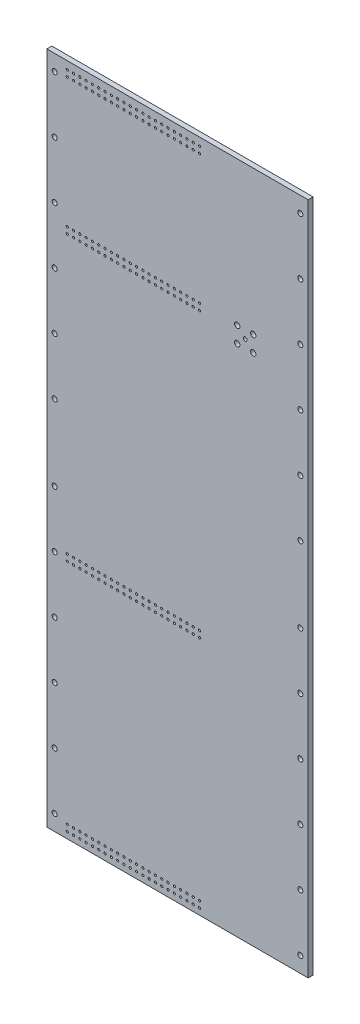
SolidWorks part; units mm, degrees
ref_plane "Front Plane" through (0, 0, 0) normal (0, 0, 1) x (1, 0, 0)
ref_plane "Top Plane" through (0, 0, 0) normal (0, 1, 0) x (1, 0, 0)
ref_plane "Right Plane" through (0, 0, 0) normal (1, 0, 0) x (0, 0, -1)
sketch "Sketch1" plane through (0, 0, 0) normal (0, 0, 1) x (1, 0, 0)
  line L1 (-41.5, -107) -> (41.5, -107)
  line L2 (-41.5, -107) -> (-41.5, 107)
  line L3 (-41.5, 107) -> (41.5, 107)
  line L4 (41.5, -107) -> (41.5, 107)
  line L5 (-41.5, -107) -> (41.5, 107) construction
  line L6 (-41.5, 107) -> (41.5, -107) construction
  point P0 (0, 0)
  dimension "D1" = 83
  dimension "D2" = 214
extrude "Boss-Extrude1" add sketch "Sketch1" along normal blind 1.5875
hole_wizard "#0 Clearance Hole1" positions "Sketch5" profile "Sketch3" hole size "#0" standard "ANSI Inch"
sketch "Sketch5" plane through (0, 0, 1.5875) normal (0, 0, 1) x (1, 0, 0)
  line L0 (0, 0) -> (0, 107) construction
  line L1 (41.5, 107) -> (-41.5, 107) construction
  line L4 (-41.5, 107) -> (-41.5, -107) construction
  line L5 (-41.5, 0) -> (41.5, 0) construction
  line L6 (41.5, -107) -> (41.5, 107) construction
  line L8 (-41.5, 7) -> (41.5, 7) construction
  line L9 (-41.5, 7) -> (-41.5, 107) construction
  line L10 (-41.5, 107) -> (41.5, 107) construction
  line L11 (41.5, 7) -> (41.5, 107) construction
  point P490 (-39, 102)
  point P557 (39, 102)
  point P558 (39, 84)
  point P559 (39, 66)
  point P560 (39, 48)
  point P561 (39, 30)
  point P562 (39, 12)
  point P563 (-39, 84)
  point P564 (-39, 66)
  point P565 (-39, 48)
  point P566 (-39, 30)
  point P567 (-39, 12)
  dimension "D1" = 2.5
  dimension "D2" = 6
  dimension "D4" = 2.5
  dimension "D3" = 2
  dimension "D5" = 100
  dimension "D6" = 5
  dimension "D7" = 5
sketch "Sketch3" plane through (-39, 102, 1.5875) normal (1, 0, 0) x (0, -1, 0)
  line L0 (0, 0) -> (0, 3.6596)
  line L1 (0, 3.6596) -> (0.8064, 3.175)
  line L2 (0.8064, 3.175) -> (0.8064, 0)
  line L5 (0.8064, 0) -> (0, 0)
  line L10 (0, 3.6596) -> (-0.8065, 3.175) construction
  line L11 (0, -6.35) -> (0, 107.95) construction
  dimension "Hole Dia." = 1.6129
  dimension "Hole Depth" = 3.175
  dimension "Drill Angle" = 118
sketch "Sketch6" plane through (0, 0, 0) normal (0, 0, -1) x (-1, 0, 0)
  line L0 (41.5, -7) -> (-41.5, -7) construction
  line L1 (-36.2, 0) -> (36.3, 0)
  line L2 (-36.2, 0) -> (-36.2, -7)
  line L3 (-36.2, -7) -> (36.3, -7)
  line L4 (36.3, 0) -> (36.3, -7)
  dimension "D1" = 72.5
extrude "Boss-Extrude3" add sketch "Sketch6" along normal blind 4.9125
sketch "Sketch7" plane through (0, 0, 1.5875) normal (0, 0, 1) x (1, 0, 0)
  line L0 (0, 107) -> (0, -107) construction
  line L1 (41.5, 107) -> (-41.5, 107) construction
  line L2 (-41.5, -107) -> (41.5, -107) construction
  line L3 (-36, 62.325) -> (8, 62.325) construction
  line L4 (-36, 105.5) -> (8, 105.5) construction
  line L5 (-36, 105.5) -> (-36, 101.5) construction
  line L6 (-36, 101.5) -> (8, 101.5) construction
  line L7 (8, 105.5) -> (8, 101.5) construction
  line L8 (-36, 62.325) -> (-36, 58.325) construction
  line L9 (-36, 58.325) -> (8, 58.325) construction
  line L10 (8, 62.325) -> (8, 58.325) construction
  line L11 (-36, 60.325) -> (41.5, 60.325) construction
  line L12 (41.5, -107) -> (41.5, 107) construction
  line L13 (-36, -27.675) -> (8, -27.675) construction
  line L14 (18, 62.206) -> (25, 62.206) construction
  line L15 (18, 62.206) -> (18, 55.206) construction
  line L16 (18, 55.206) -> (25, 55.206) construction
  line L17 (25, 62.206) -> (25, 55.206) construction
  line L18 (-36, -27.675) -> (-36, -31.675) construction
  line L19 (-36, -31.675) -> (8, -31.675) construction
  line L20 (8, -27.675) -> (8, -31.675) construction
  line L21 (-36, -102) -> (8, -102) construction
  line L22 (-36, -102) -> (-36, -106) construction
  line L23 (-36, -106) -> (8, -106) construction
  line L24 (8, -102) -> (8, -106) construction
  circle A0 centre (-35, 102.5) radius 0.35
  circle A1 centre (-33, 102.5) radius 0.35
  circle A2 centre (-31, 102.5) radius 0.35
  circle A3 centre (-29, 102.5) radius 0.35
  circle A4 centre (-27, 102.5) radius 0.35
  circle A5 centre (-25, 102.5) radius 0.35
  circle A6 centre (-23, 102.5) radius 0.35
  circle A7 centre (-21, 102.5) radius 0.35
  circle A8 centre (-19, 102.5) radius 0.35
  circle A9 centre (-17, 102.5) radius 0.35
  circle A10 centre (-15, 102.5) radius 0.35
  circle A11 centre (-13, 102.5) radius 0.35
  circle A12 centre (-11, 102.5) radius 0.35
  circle A13 centre (-9, 102.5) radius 0.35
  circle A14 centre (-7, 102.5) radius 0.35
  circle A15 centre (-5, 102.5) radius 0.35
  circle A16 centre (-3, 102.5) radius 0.35
  circle A17 centre (-1, 102.5) radius 0.35
  circle A18 centre (1, 102.5) radius 0.35
  circle A19 centre (3, 102.5) radius 0.35
  circle A20 centre (5, 102.5) radius 0.35
  circle A21 centre (7, 102.5) radius 0.35
  circle A22 centre (-33, 104.5) radius 0.35
  circle A23 centre (-31, 104.5) radius 0.35
  circle A24 centre (-29, 104.5) radius 0.35
  circle A25 centre (-27, 104.5) radius 0.35
  circle A26 centre (-25, 104.5) radius 0.35
  circle A27 centre (-23, 104.5) radius 0.35
  circle A28 centre (-21, 104.5) radius 0.35
  circle A29 centre (-19, 104.5) radius 0.35
  circle A30 centre (-17, 104.5) radius 0.35
  circle A31 centre (-15, 104.5) radius 0.35
  circle A32 centre (-13, 104.5) radius 0.35
  circle A33 centre (-11, 104.5) radius 0.35
  circle A34 centre (-9, 104.5) radius 0.35
  circle A35 centre (-7, 104.5) radius 0.35
  circle A36 centre (-5, 104.5) radius 0.35
  circle A37 centre (-3, 104.5) radius 0.35
  circle A38 centre (-1, 104.5) radius 0.35
  circle A39 centre (1, 104.5) radius 0.35
  circle A40 centre (3, 104.5) radius 0.35
  circle A41 centre (5, 104.5) radius 0.35
  circle A42 centre (7, 104.5) radius 0.35
  circle A43 centre (-35, 104.5) radius 0.35
  circle A44 centre (-35, 59.325) radius 0.35
  circle A45 centre (-33, 59.325) radius 0.35
  circle A46 centre (-31, 59.325) radius 0.35
  circle A47 centre (-29, 59.325) radius 0.35
  circle A48 centre (-27, 59.325) radius 0.35
  circle A49 centre (-25, 59.325) radius 0.35
  circle A50 centre (-23, 59.325) radius 0.35
  circle A51 centre (-21, 59.325) radius 0.35
  circle A52 centre (-19, 59.325) radius 0.35
  circle A53 centre (-17, 59.325) radius 0.35
  circle A54 centre (-15, 59.325) radius 0.35
  circle A55 centre (-13, 59.325) radius 0.35
  circle A56 centre (-11, 59.325) radius 0.35
  circle A57 centre (-9, 59.325) radius 0.35
  circle A58 centre (-7, 59.325) radius 0.35
  circle A59 centre (-5, 59.325) radius 0.35
  circle A60 centre (-3, 59.325) radius 0.35
  circle A61 centre (-1, 59.325) radius 0.35
  circle A62 centre (1, 59.325) radius 0.35
  circle A63 centre (3, 59.325) radius 0.35
  circle A64 centre (5, 59.325) radius 0.35
  circle A65 centre (7, 59.325) radius 0.35
  circle A66 centre (-33, 61.325) radius 0.35
  circle A67 centre (-31, 61.325) radius 0.35
  circle A68 centre (-29, 61.325) radius 0.35
  circle A69 centre (-27, 61.325) radius 0.35
  circle A70 centre (-25, 61.325) radius 0.35
  circle A71 centre (-23, 61.325) radius 0.35
  circle A72 centre (-21, 61.325) radius 0.35
  circle A73 centre (-19, 61.325) radius 0.35
  circle A74 centre (-17, 61.325) radius 0.35
  circle A75 centre (-15, 61.325) radius 0.35
  circle A76 centre (-13, 61.325) radius 0.35
  circle A77 centre (-11, 61.325) radius 0.35
  circle A78 centre (-9, 61.325) radius 0.35
  circle A79 centre (-7, 61.325) radius 0.35
  circle A80 centre (-5, 61.325) radius 0.35
  circle A81 centre (-3, 61.325) radius 0.35
  circle A82 centre (-1, 61.325) radius 0.35
  circle A83 centre (1, 61.325) radius 0.35
  circle A84 centre (3, 61.325) radius 0.35
  circle A85 centre (5, 61.325) radius 0.35
  circle A86 centre (7, 61.325) radius 0.35
  circle A87 centre (-35, 61.325) radius 0.35
  circle A88 centre (21.5, 58.706) radius 0.6
  circle A89 centre (18.96, 61.246) radius 0.85
  circle A90 centre (24.04, 61.246) radius 0.85
  circle A91 centre (24.04, 56.166) radius 0.85
  circle A92 centre (18.96, 56.166) radius 0.85
  circle A93 centre (21.5, 58.706) radius 0.381 construction
  circle A94 centre (-35, -30.675) radius 0.35
  circle A95 centre (-33, -30.675) radius 0.35
  circle A96 centre (-31, -30.675) radius 0.35
  circle A97 centre (-29, -30.675) radius 0.35
  circle A98 centre (-27, -30.675) radius 0.35
  circle A99 centre (-25, -30.675) radius 0.35
  circle A100 centre (-23, -30.675) radius 0.35
  circle A101 centre (-21, -30.675) radius 0.35
  circle A102 centre (-19, -30.675) radius 0.35
  circle A103 centre (-17, -30.675) radius 0.35
  circle A104 centre (-15, -30.675) radius 0.35
  circle A105 centre (-13, -30.675) radius 0.35
  circle A106 centre (-11, -30.675) radius 0.35
  circle A107 centre (-9, -30.675) radius 0.35
  circle A108 centre (-7, -30.675) radius 0.35
  circle A109 centre (-5, -30.675) radius 0.35
  circle A110 centre (-3, -30.675) radius 0.35
  circle A111 centre (-1, -30.675) radius 0.35
  circle A112 centre (1, -30.675) radius 0.35
  circle A113 centre (3, -30.675) radius 0.35
  circle A114 centre (5, -30.675) radius 0.35
  circle A115 centre (7, -30.675) radius 0.35
  circle A116 centre (-33, -28.675) radius 0.35
  circle A117 centre (-31, -28.675) radius 0.35
  circle A118 centre (-29, -28.675) radius 0.35
  circle A119 centre (-27, -28.675) radius 0.35
  circle A120 centre (-25, -28.675) radius 0.35
  circle A121 centre (-23, -28.675) radius 0.35
  circle A122 centre (-21, -28.675) radius 0.35
  circle A123 centre (-19, -28.675) radius 0.35
  circle A124 centre (-17, -28.675) radius 0.35
  circle A125 centre (-15, -28.675) radius 0.35
  circle A126 centre (-13, -28.675) radius 0.35
  circle A127 centre (-11, -28.675) radius 0.35
  circle A128 centre (-9, -28.675) radius 0.35
  circle A129 centre (-7, -28.675) radius 0.35
  circle A130 centre (-5, -28.675) radius 0.35
  circle A131 centre (-3, -28.675) radius 0.35
  circle A132 centre (-1, -28.675) radius 0.35
  circle A133 centre (1, -28.675) radius 0.35
  circle A134 centre (3, -28.675) radius 0.35
  circle A135 centre (5, -28.675) radius 0.35
  circle A136 centre (7, -28.675) radius 0.35
  circle A137 centre (-35, -28.675) radius 0.35
  circle A138 centre (-35, -105) radius 0.35
  circle A139 centre (-33, -105) radius 0.35
  circle A140 centre (-31, -105) radius 0.35
  circle A141 centre (-29, -105) radius 0.35
  circle A142 centre (-27, -105) radius 0.35
  circle A143 centre (-25, -105) radius 0.35
  circle A144 centre (-23, -105) radius 0.35
  circle A145 centre (-21, -105) radius 0.35
  circle A146 centre (-19, -105) radius 0.35
  circle A147 centre (-17, -105) radius 0.35
  circle A148 centre (-15, -105) radius 0.35
  circle A149 centre (-13, -105) radius 0.35
  circle A150 centre (-11, -105) radius 0.35
  circle A151 centre (-9, -105) radius 0.35
  circle A152 centre (-7, -105) radius 0.35
  circle A153 centre (-5, -105) radius 0.35
  circle A154 centre (-3, -105) radius 0.35
  circle A155 centre (-1, -105) radius 0.35
  circle A156 centre (1, -105) radius 0.35
  circle A157 centre (3, -105) radius 0.35
  circle A158 centre (5, -105) radius 0.35
  circle A159 centre (7, -105) radius 0.35
  circle A160 centre (-33, -103) radius 0.35
  circle A161 centre (-31, -103) radius 0.35
  circle A162 centre (-29, -103) radius 0.35
  circle A163 centre (-27, -103) radius 0.35
  circle A164 centre (-25, -103) radius 0.35
  circle A165 centre (-23, -103) radius 0.35
  circle A166 centre (-21, -103) radius 0.35
  circle A167 centre (-19, -103) radius 0.35
  circle A168 centre (-17, -103) radius 0.35
  circle A169 centre (-15, -103) radius 0.35
  circle A170 centre (-13, -103) radius 0.35
  circle A171 centre (-11, -103) radius 0.35
  circle A172 centre (-9, -103) radius 0.35
  circle A173 centre (-7, -103) radius 0.35
  circle A174 centre (-5, -103) radius 0.35
  circle A175 centre (-3, -103) radius 0.35
  circle A176 centre (-1, -103) radius 0.35
  circle A177 centre (1, -103) radius 0.35
  circle A178 centre (3, -103) radius 0.35
  circle A179 centre (5, -103) radius 0.35
  circle A180 centre (7, -103) radius 0.35
  circle A181 centre (-35, -103) radius 0.35
  dimension "D1" = 0.7
  dimension "D14" = 1.2
  dimension "D15" = 1.7
  dimension "D27" = 0.762
  dimension "D4" = 2
  dimension "D5" = 42
  dimension "D6" = 1
  dimension "D7" = 1
  dimension "D8" = 4
  dimension "D9" = 44
  dimension "D10" = 1
  dimension "D11" = 2.5
  dimension "D12" = 2
  dimension "D13" = 1
  dimension "D16" = 2.54
  dimension "D17" = 2.54
  dimension "D20" = 5.08
  dimension "D21" = 5.08
  dimension "D22" = 7
  dimension "D23" = 3.5
  dimension "D24" = 3.5
  dimension "D25" = 48.675
  dimension "D26" = 10
  dimension "D29" = 1
  dimension "D30" = 90
  dimension "D32" = 1
  dimension "D33" = 1
  dimension "D2" = 22
  dimension "D3" = 2
  dimension "D18" = 2
  dimension "D19" = 2
  dimension "D28" = 2
  dimension "D31" = 2
extrude "Cut-Extrude1" cut sketch "Sketch7" against normal through all
mirror "Mirror1" about plane through (0, 0, 0) normal (0, 1, 0) of "#0 Clearance Hole1"
